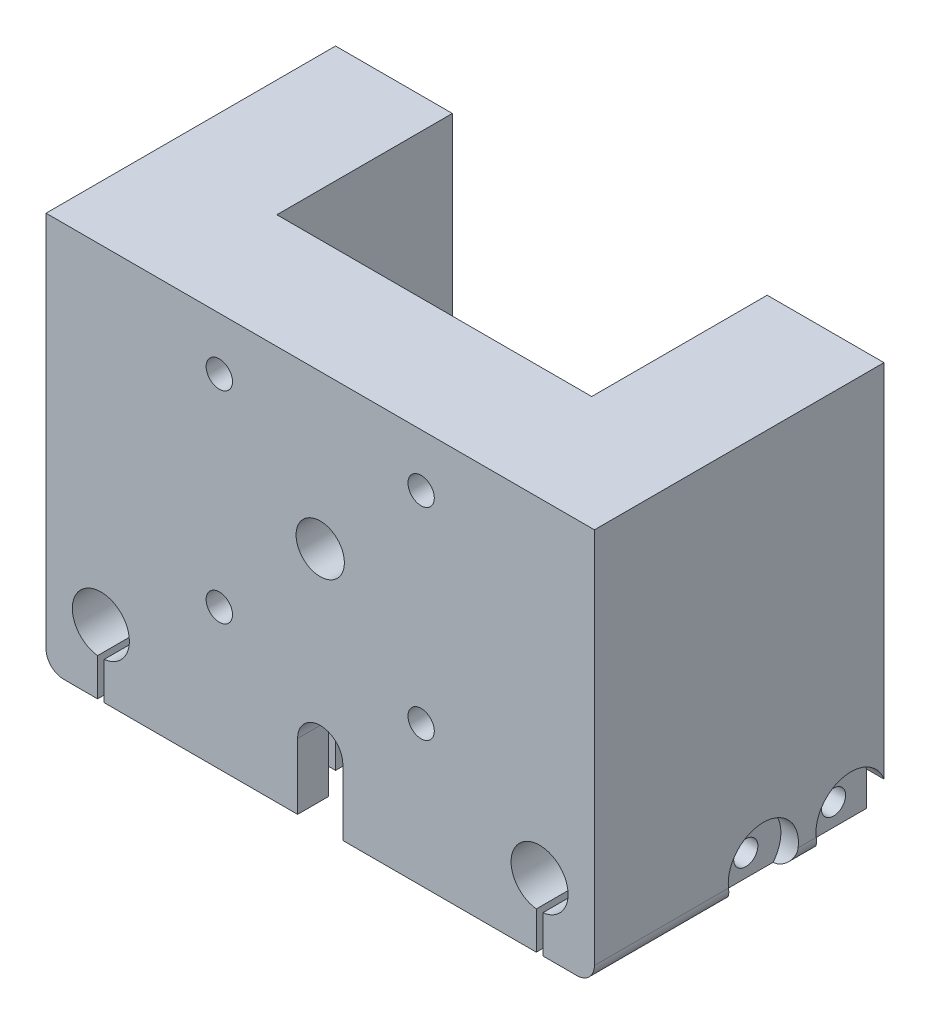
SolidWorks part; units mm, degrees
ref_plane "Front Plane" through (0, 0, 0) normal (0, 0, 1) x (1, 0, 0)
ref_plane "Top Plane" through (0, 0, 0) normal (0, 1, 0) x (1, 0, 0)
ref_plane "Right Plane" through (0, 0, 0) normal (1, 0, 0) x (0, 0, -1)
sketch "Sketch1" plane through (0, 0, 0) normal (0, 0, 1) x (1, 0, 0)
  line L1 (-31.25, 0) -> (31.25, 0)
  line L2 (-31.25, 0) -> (-31.25, 45)
  line L3 (-31.25, 45) -> (31.25, 45)
  line L4 (31.25, 0) -> (31.25, 45)
  point P4 (0, 0)
  dimension "D1" = 62.5
  dimension "D2" = 45
extrude "Boss-Extrude1" add sketch "Sketch1" along normal blind 20
sketch "Sketch2" plane through (0, 0, 20) normal (0, 0, 1) x (1, 0, 0)
  line L0 (31.25, 45) -> (-31.25, 45) construction
  line L1 (-18.75, 45) -> (18.75, 45)
  line L2 (-18.75, 45) -> (-18.75, 0)
  line L3 (-18.75, 0) -> (18.75, 0)
  line L4 (18.75, 45) -> (18.75, 0)
  line L5 (-31.25, 0) -> (31.25, 0) construction
  line L6 (-31.25, 45) -> (-31.25, 0) construction
  point P8 (0, 0)
  dimension "D1" = 37.5
extrude "Cut-Extrude1" cut sketch "Sketch2" against normal offset from surface (5 mm away) 15 up to face at (0, 22.5, 0)
sketch "Sketch3" plane through (0, 0, 0) normal (0, 0, -1) x (-1, 0, 0)
  line L0 (0, 45) -> (0, 0) construction
  line L3 (-31.25, 45) -> (31.25, 45) construction
  circle A0 centre (0, 27.5) radius 11.5
  dimension "D1" = 23
  dimension "D2" = 17.5
extrude "Cut-Extrude2" cut sketch "Sketch3" against normal blind 2
sketch "Sketch4" plane through (0, 0, 0) normal (0, 0, -1) x (-1, 0, 0)
  circle A0 centre (11.5, 39) radius 1.5
  circle A1 centre (0, 27.5) radius 11.5 construction
  circle A2 centre (0, 27.5) radius 11.5 construction
  dimension "D3" = 3
  dimension "D1" = 11.5
  dimension "D2" = 11.5
extrude "Cut-Extrude3" cut sketch "Sketch4" against normal up to surface (15 mm away) up to face at (0, 22.5, 15)
pattern_circular "CirPattern1" count 4 over 360 about axis through (0, 27.5, 0) along (0, 0, -1) of "Cut-Extrude3"
sketch "Sketch5" plane through (0, 0, 2) normal (0, 0, -1) x (-1, 0, 0)
  circle A0 centre (0, 27.5) radius 2.75
  dimension "D1" = 5.5
extrude "Cut-Extrude4" cut sketch "Sketch5" against normal through all
sketch "Sketch8" plane through (0, 0, 0) normal (0, 0, -1) x (-1, 0, 0)
  line L0 (0, 0) -> (0, 45) construction
  line L1 (7.125, 0) -> (-7.125, 0)
  line L2 (7.125, 0) -> (7.125, 11.75)
  line L3 (5.125, 13.75) -> (-5.125, 13.75)
  line L4 (-7.125, 0) -> (-7.125, 11.75)
  line L5 (-31.25, 45) -> (31.25, 45) construction
  line L6 (31.25, 0) -> (-31.25, 0) construction
  arc A1 (-5.125, 13.75) -> (-7.125, 11.75) centre (-5.125, 11.75) ccw
  arc A2 (7.125, 11.75) -> (5.125, 13.75) centre (5.125, 11.75) ccw
  point P9 (0, 0)
  point P17 (-7.125, 13.75)
  point P20 (7.125, 13.75)
  dimension "D3" = 2
  dimension "D1" = 14.25
  dimension "D2" = 13.75
extrude "Cut-Extrude7" cut sketch "Sketch8" against normal blind 3 from offset 6.5 offset against normal yes
sketch "Sketch9" plane through (0, 0, 0) normal (0, 0, -1) x (-1, 0, 0)
  line L0 (4.75, 7.5) -> (4.75, 0)
  line L1 (31.25, 0) -> (-31.25, 0) construction
  line L2 (4.75, 0) -> (-4.75, 0)
  line L3 (-4.75, 0) -> (-4.75, 7.5)
  line L6 (25, 7.5) -> (-25, 7.5) construction
  arc A0 (-4.75, 7.5) -> (4.75, 7.5) centre (0, 7.5) cw
  dimension "D1" = 4.75
  dimension "D2" = 7.5
extrude "Cut-Extrude8" cut sketch "Sketch9" against normal up to surface (6.5 mm away) up to face at (0, 8.6381, 6.5)
sketch "Sketch10" plane through (0, 0, 15) normal (0, 0, 1) x (1, 0, 0)
  line L0 (2.575, 7.5) -> (2.575, 0)
  line L1 (-18.75, 0) -> (18.75, 0) construction
  line L2 (2.575, 0) -> (-2.575, 0)
  line L3 (-2.575, 0) -> (-2.575, 7.5)
  line L4 (25, 7.5) -> (-25, 7.5) construction
  arc A0 (-2.575, 7.5) -> (2.575, 7.5) centre (0, 7.5) cw
  dimension "D1" = 2.575
  dimension "D2" = 7.5
  dimension "D3" = 50
extrude "Cut-Extrude9" cut sketch "Sketch10" against normal up to surface (5.5 mm away) up to face at (0, 8.6381, 9.5)
sketch "Sketch11" plane through (31.25, 0, 0) normal (1, 0, 0) x (0, 0, -1)
  line L0 (-20, 0) -> (0, 0) construction
  line L1 (-20, 0) -> (-20, 45) construction
  circle A0 centre (-17.5, 2.5) radius 1.375
  dimension "D1" = 2.75
  dimension "D2" = 2.5
  dimension "D3" = 2.5
extrude "Cut-Extrude10" cut sketch "Sketch11" against normal through all
fillet "Fillet1" radius 2 2 edges at (-31.25, 0, 10) (31.25, 0, 10)
sketch "Sketch12" plane through (31.25, 0, 0) normal (1, 0, 0) x (0, 0, -1)
  circle A0 centre (-17.5, 2.5) radius 3.625
  dimension "D1" = 7.25
extrude "Cut-Extrude12" cut sketch "Sketch12" against normal blind 3
mirror "Mirror3" about plane through (0, 0, 0) normal (1, 0, 0) of "Cut-Extrude12"
sketch "Sketch13" plane through (0, 0, 0) normal (0, 0, -1) x (-1, 0, 0)
  line L0 (29.25, 0) -> (4.75, 0) construction
  line L1 (17.9399, 0) -> (29.25, 0)
  line L2 (17.9399, 0) -> (17.9399, 45)
  line L3 (17.9399, 45) -> (31.25, 45)
  line L4 (31.25, 2) -> (31.25, 45)
  arc A0 (31.25, 2) -> (29.25, 0) centre (29.25, 2) cw
  dimension "D1" = 2
extrude "Boss-Extrude2" add sketch "Sketch13" along normal blind 20
sketch "Sketch14" plane through (-31.25, 0, 0) normal (-1, 0, 0) x (0, 0, 1)
  line L0 (14.875, 0) -> (-20, 0) construction
  line L3 (-20.25, 2.5) -> (-20.25, -1.1785)
  line L4 (-20.25, -1.1785) -> (-17.8212, -1.1785)
  line L5 (-20, 2) -> (-20, 45) construction
  circle A0 centre (-6.25, 2.5) radius 4
  circle A1 centre (-16.25, 2.5) radius 4
  line M6 (-20, 45) -> (-20, 2)
  line M7 (-20, 2) -> (13.9096, 2)
  dimension "D2" = 8
  dimension "D1" = 2.5
  dimension "D3" = 2.5
  dimension "D4" = 10
  dimension "D5" = 3.75
extrude "Cut-Extrude18" cut sketch "Sketch14" against normal blind 2 contours A1 M6 M7 | A1 M7 M6 | A1 L3 L4 | A0 region at (-31.25, -0.3234, -19.5854) region at (-31.25, 0.5658, -16.3134) region at (-31.25, 3.9452, -16.2026)
sketch "Sketch15" plane through (0, 0, 20) normal (0, 0, 1) x (1, 0, 0)
  line L1 (31.25, 45) -> (-31.25, 45)
  line L2 (31.25, 45) -> (31.25, 0)
  line L3 (31.25, 0) -> (-31.25, 0)
  line L4 (-31.25, 45) -> (-31.25, 0)
extrude "Cut-Extrude19" cut sketch "Sketch15" against normal blind 7
sketch "Sketch16" plane through (0, 0, 13) normal (0, 0, 1) x (1, 0, 0)
  line L1 (-24.625, 4.2717) -> (-24.625, 0)
  line L2 (-29.25, 0) -> (-2.575, 0) construction
  line L3 (-24.625, 0) -> (-25.375, 0)
  line L4 (-25.375, 0) -> (-25.375, 4.2717)
  line L5 (-31.25, 45) -> (-31.25, 2) construction
  circle A0 centre (-25, 7.5) radius 3.25
  circle A1 centre (0, 27.5) radius 2.75 construction
  line M5 (-29.25, 0) -> (-2.575, 0)
  dimension "D1" = 20
  dimension "D2" = 6.5
  dimension "D3" = 6.25
  dimension "D4" = 0.75
  dimension "D5" = 0.375
extrude "Cut-Extrude20" cut sketch "Sketch16" against normal through all contours A0 L4 L1 M5 | A0 region at (-25, 2.1286, 13) region at (-25, 7.5, 13)
mirror "Mirror4" about plane through (0, 0, 0) normal (1, 0, 0) of "Cut-Extrude20", "Boss-Extrude2", "Cut-Extrude18"
sketch "Sketch17" plane through (-29.25, 0, 0) normal (-1, 0, 0) x (0, 0, 1)
  circle A0 centre (-6.25, 2.5) radius 1.375
  circle A1 centre (-16.25, 2.5) radius 1.375
  dimension "D1" = 2.75
extrude "Cut-Extrude21" cut sketch "Sketch17" against normal through all
